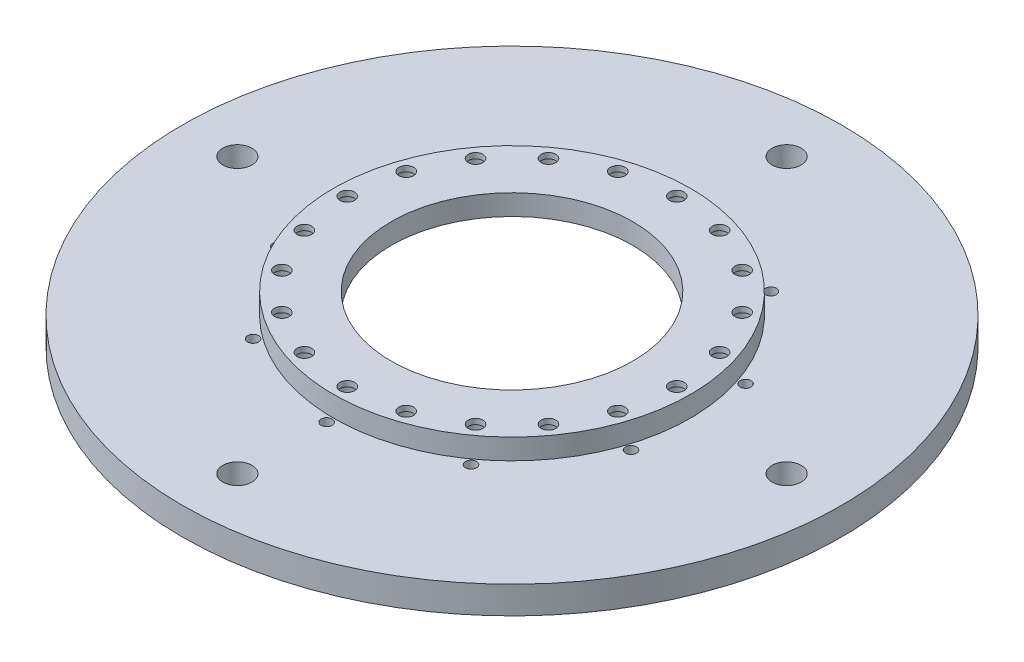
SolidWorks part; units mm, degrees
material "Plain Carbon Steel"
ref_plane "Front Plane" through (0, 0, 0) normal (0, 0, 1) x (1, 0, 0)
ref_plane "Top Plane" through (0, 0, 0) normal (0, 1, 0) x (1, 0, 0)
ref_plane "Right Plane" through (0, 0, 0) normal (1, 0, 0) x (0, 0, -1)
sketch "Sketch9" plane through (0, 0, 0) normal (0, 1, 0) x (1, 0, 0)
  circle A2 centre (0, 0) radius 82.55
  circle A4 centre (0, 0) radius 55.88
  circle A5 centre (0, 0) radius 76.2 construction
  point P6 (0, 76.2)
  point P34 (0, 0)
  dimension "Diameter_BackPlate" = 165.1
  dimension "Diameter_FuelOuterPlenum" = 111.76
  dimension "Diameter_BackPlate_BoltCircle" = 152.4
extrude "REF_BackPlate" add sketch "Sketch9" along normal blind 9.525 contours A2 A4 region at (-80.2151, 0, 0)
sketch "Sketch1" plane through (0, 0, 0) normal (0, 1, 0) x (1, 0, 0)
  line L1 (0, 82.55) -> (0, 81.788) construction
  line L2 (0, 81.788) -> (0, 76.2) construction
  line L6 (8.7416, 55.192) -> (13.4103, 84.6696) construction
  line L7 (0, 82.55) -> (0, 127) construction
  line L8 (39.2452, 120.7842) -> (25.5094, 78.5097) construction
  line L9 (8.7416, 55.192) -> (0, 0) construction
  circle A3 centre (0, 0) radius 152.4
  circle A8 centre (0, 0) radius 127 construction
  circle A14 centre (0, 76.2) radius 5.588 construction
  circle A15 centre (0, 0) radius 55.88 construction
  circle A17 centre (0, 0) radius 82.55 construction
  circle A18 centre (23.5471, 72.4705) radius 5.588 construction
  circle A19 centre (0, 0) radius 76.2 construction
  circle A20 centre (0, 0) radius 79.375
  circle A23 centre (0, 0) radius 85.725 construction
  arc A24 (0, 76.2) -> (23.5471, 72.4705) centre (0, 0) cw construction
  point P2 (0, 127)
  point P5 (0, 85.725)
  point P12 (11.9203, 75.2619)
  dimension "Diameter_Takeout_BoltCircle" = 254
  dimension "Diameter_ThrustPlate" = 304.8
  dimension "D1" = 11.176
  dimension "D2" = 171.45
  dimension "D4" = 158.75
  dimension "D3" = 18
sketch "Sketch20" plane through (0, 0, 0) normal (0, -1, 0) x (-1, 0, 0)
  point P0 (0, 76.2)
hole_wizard "REF_CBORE_BackPlate" positions "Sketch20" profile "Sketch21" counterbore size "1/4" standard "ANSI Inch" end condition through all
sketch "Sketch21" plane through (0, 0, -76.2) normal (1, 0, 0) x (0, 0, -1)
  line L0 (0, 0) -> (0, 9.525)
  line L1 (0, 9.525) -> (3.3782, 9.525)
  line L3 (3.3782, 9.525) -> (3.3782, 6.985)
  line L4 (3.3782, 6.985) -> (5.588, 6.985)
  line L5 (5.588, 6.985) -> (5.588, 0)
  line L7 (5.588, 0) -> (0, 0)
  line L11 (0, -6.35) -> (0, 107.95) construction
  dimension "Thru Hole Dia." = 6.7564
  dimension "Thru Hole Depth" = 9.525
  dimension "C'Bore Dia." = 11.176
  dimension "C'Bore Depth" = 6.985
pattern_circular "REF_CBORE_BackPlate_Pattern" count 20 over 360 about axis through (0, 9.525, 0) along (0, -1, 0) of "REF_CBORE_BackPlate"
extrude "ThrustPlate_TC3" add sketch "Sketch1" against normal blind 12.7 separate body contours A3 region at (-148.0895, 0, 0)
sketch "Sketch11" plane through (0, 0, 0) normal (0, 1, 0) x (1, 0, 0)
  point P0 (0, 127)
hole_wizard "UNDEF_Clearance_ThrustPlate" positions "Sketch11" profile "Sketch12" hole size "1/2" standard "ANSI Inch" end condition through all
sketch "Sketch12" plane through (0, 0, -127) normal (1, 0, 0) x (0, 0, 1)
  line L0 (0, 0) -> (0, 12.7)
  line L1 (0, 12.7) -> (6.7462, 12.7)
  line L2 (6.7462, 12.7) -> (6.7462, 0)
  line L5 (6.7462, 0) -> (0, 0)
  line L11 (0, -6.35) -> (0, 107.95) construction
  dimension "Thru Hole Dia." = 13.4925
  dimension "Thru Hole Depth" = 12.7
pattern_circular "Clearance_ThrustPlate_Pattern" count 4 over 360 about axis through (0, -12.7, 0) along (0, 1, 0) of "UNDEF_Clearance_ThrustPlate" reverse direction yes
sketch "Sketch22" plane through (0, 0, 0) normal (0, 1, 0) x (1, 0, 0)
  point P0 (0, 85.725)
hole_wizard "#10 Clearance Hole1" positions "Sketch22" profile "Sketch23" hole size "#10" standard "ANSI Inch" end condition through all
sketch "Sketch23" plane through (0, 0, -85.725) normal (1, 0, 0) x (0, 0, 1)
  line L0 (0, 0) -> (0, 12.7)
  line L1 (0, 12.7) -> (2.5527, 12.7)
  line L2 (2.5527, 12.7) -> (2.5527, 0)
  line L5 (2.5527, 0) -> (0, 0)
  line L11 (0, -6.35) -> (0, 107.95) construction
  dimension "Thru Hole Dia." = 5.1054
  dimension "Thru Hole Depth" = 12.7
pattern_circular "CirPattern1" count 10 over 360 about axis through (0, -12.7, 0) along (0, 1, 0) of "#10 Clearance Hole1" reverse direction yes
equation "\"Diameter_BackPlate\"= 6.5"
equation "\"VAR_Diameter_BackPlate_BoltCircle\"= 6"
equation "\"VAR_Diameter_FuelOuterPlenum\"= 4.4"
equation "\"Diameter_BackPlate@Sketch9\"=\"Diameter_BackPlate\""
equation "\"Diameter_BackPlate_BoltCircle@Sketch9\"=\"VAR_Diameter_BackPlate_BoltCircle\""
equation "\"Diameter_FuelOuterPlenum@Sketch9\"=\"VAR_Diameter_FuelOuterPlenum\""
equation "\"Thickness_ThrustPlate\"= 0.5'undetermined"
equation "\"Diameter_ThrustPlate\"= 12'defined"
equation "\"Diameter_Takeout_BoltCicle\"= 10'defined"
equation "\"Diameter_Takeout_BoltCircle@Sketch1\"=\"Diameter_Takeout_BoltCicle\""
equation "\"Diameter_ThrustPlate@Sketch1\"=\"Diameter_ThrustPlate\""
equation "\"D1@ThrustPlate_TC3\"=\"Thickness_ThrustPlate\""
equation "\"VAR_Diameter_CBORE\"= 0.44'undetermined"
equation "\"VAR_Diameter_Clearance_ThrustPlate\"= 0.25'undetermined"
equation "\"D3@Sketch1\"=360/\"D1@REF_CBORE_BackPlate_Pattern\""
equation "\"D1@Sketch1\"=\"C'Bore Dia.@Sketch21\"''''''''''''''''''''''''''''''''''''''''''''''''''''''''''''''''''''"
equation "\"C'Bore Dia.@Sketch21\"=\"VAR_Diameter_CBORE\""
equation "\"NumberBolts_BackPlate\"= 20"
equation "\"NumberBolts_Takeout\"= 4'defined"
equation "\"D1@Clearance_ThrustPlate_Pattern\"=\"NumberBolts_Takeout\""
equation "\"D1@REF_CBORE_BackPlate_Pattern\"=\"NumberBolts_BackPlate\""
